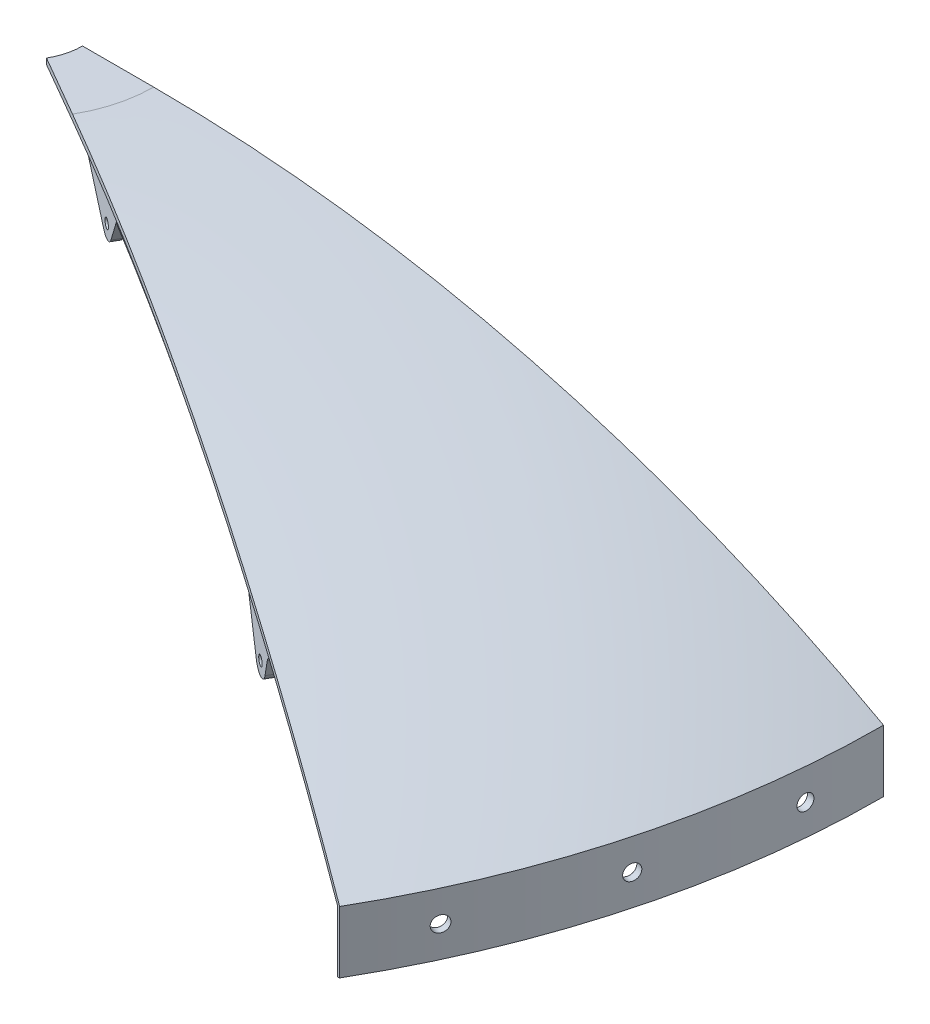
SolidWorks part; units mm, degrees
note: '?' marks a value the reader was unsure of.
other "Markup1"
sketch "Sketch6" plane through (25, -0.5009, 1.5) normal (-0.1086, 0.112, 0.9878) x (0.8685, -0.4727, 0.1491)
ref_plane "Front Plane" through (0, 0, 0) normal (0, 0, 1) x (1, 0, 0)
ref_plane "Top Plane" through (0, 0, 0) normal (0, 1, 0) x (1, 0, 0)
ref_plane "Right Plane" through (0, 0, 0) normal (1, 0, 0) x (0, 0, -1)
sketch "Sketch1" plane through (0, 0, 0) normal (0, 0, 1) x (1, 0, 0)
  line L0 (-45, 0) -> (45, 0) construction
  line L1 (300, -65.3534) -> (300, -85.3534)
  line L2 (-45, -150.7069) -> (45, -150.7069) construction
  line L3 (-45, 0) -> (-45, -150.7069) construction
  line L4 (45, 0) -> (45, -150.7069) construction
  line L5 (0, 0) -> (0, -150.7069)
  line L6 (45, 0) -> (0, 0)
  line L7 (0, -150.7069) -> (45, -150.7069)
  arc A0 (45, 0) -> (300, -65.3534) centre (45, -530.1639) cw
  arc A1 (-28.1177, 0) -> (35.3823, 0) centre (3.6323, -0.0236) cw construction
  arc A2 (45, -150.7069) -> (300, -85.3534) centre (45, 379.457) ccw
  point P4 (0, 0)
  dimension "D2" = 300
  dimension "D3" = 31.75
  dimension "D5" = 150.7069
  dimension "D1" = 90
  dimension "D4" = 20
sketch "Sketch2" plane through (0, 0, 0) normal (0, 0, 1) x (1, 0, 0)
  line L0 (299.5, -67.3534) -> (293.5, -67.3534)
  line L1 (291.5, -69.3534) -> (291.5, -85.6495)
  line L2 (54.9033, -10.5962) -> (27, -10.5962)
  line L3 (25, -8.5962) -> (25, -5.5)
  line L4 (300, -65.3534) -> (300, -85.3534) construction
  line L5 (300, -65.3534) -> (300, -85.3534) construction
  line L6 (299.5, -65.6495) -> (299.5, -67.3534)
  line L7 (291.5, -85.6495) -> (271.5, -85.6495)
  line L8 (45, -1.5009) -> (45, -3.5)
  line L9 (45, 0) -> (45, -150.7069) construction
  line L10 (45, -3.5) -> (27, -3.5)
  line L11 (271.5, -85.6495) -> (271.5, -65.6032)
  line L12 (45, -0.5) -> (0.5, -0.5)
  line L13 (0.5, -0.5) -> (0.5, -150.2069)
  line L14 (0.5, -150.2069) -> (45, -150.2069)
  line L15 (299.5, -85.0574) -> (299.5, -65.6495)
  line L20 (55, -13.5) -> (25, -13.5) construction
  line L21 (55, -10.5962) -> (55, -13.5) construction
  line L22 (140, -19.2573) -> (140, -23.2573)
  line L23 (140, -19.2573) -> (126, -19.2573)
  line L24 (125, -18.2573) -> (125, -17.5517)
  line L25 (141, -24.2573) -> (163.7816, -24.2573)
  line L26 (0, 0) -> (0, -150.7069) construction
  line L27 (45, -3.5) -> (25, -3.5) construction
  line L28 (45, -0.5) -> (45, -3.5) construction
  arc A0 (268.6519, -61.0899) -> (163.7816, -24.2573) centre (45, -530.1639) ccw
  arc A1 (294.6951, -74.4195) -> (55, -10.5962) centre (45, -530.1639) ccw construction
  arc A2 (55.0976, -10.5981) -> (54.9033, -10.5962) centre (54.9033, -20.5962) ccw
  arc A3 (271.5, -65.6032) -> (268.6519, -61.0899) centre (266.5, -65.6032) ccw
  arc A4 (293.5, -67.3534) -> (291.5, -69.3534) centre (293.5, -69.3534) ccw
  arc A5 (124.1523, -16.5634) -> (55.0976, -10.5981) centre (45, -530.1639) ccw
  arc A6 (45, -150.2069) -> (299.5, -85.0574) centre (45, 379.457) ccw
  arc A7 (299.5, -65.6495) -> (45, -0.5) centre (45, -530.1639) ccw
  arc A9 (299.5, -65.6495) -> (46.0019, -0.5009) centre (45, -530.1639) ccw
  arc A10 (125, -16.6947) -> (163.7816, -24.2573) centre (45, -530.1639) cw construction
  arc A11 (140, -23.2573) -> (141, -24.2573) centre (141, -23.2573) ccw
  arc A12 (126, -19.2573) -> (125, -18.2573) centre (126, -18.2573) cw
  arc A13 (125, -17.5517) -> (124.1523, -16.5634) centre (124, -17.5517) ccw
  arc A14 (27, -10.5962) -> (25, -8.5962) centre (27, -8.5962) cw
  arc A15 (27, -3.5) -> (25, -5.5) centre (27, -5.5) ccw
  arc A16 (299.5, -65.6495) -> (45, -0.5) centre (45, -530.1639) ccw construction
  arc A17 (45, -1.5009) -> (46.0019, -0.5009) centre (46, -1.5009) cw
  point P26 (300, -75.3534)
  point P33 (291.5, -67.3534)
  point P43 (140, -24.2573)
  point P48 (125, -19.2573)
  point P57 (25, -3.5)
  dimension "D5" = 10
  dimension "D10" = 5
  dimension "D11" = 2
  dimension "D16" = 1
  dimension "D17" = 2
  dimension "D18" = 1
  dimension "D2" = 20
  dimension "D3" = 3
  dimension "D6" = 7.0962
  dimension "D7" = 8
  dimension "D8" = 8
  dimension "D9" = 20
  dimension "D12" = 20
  dimension "D13" = 15
  dimension "D14" = 5
  dimension "D15" = 140
  dimension "D1" = 0.5
  dimension "D4" = 10
sketch "Sketch7" plane through (0, 0, 0) normal (0, 0, 1) x (1, 0, 0)
  line L4 (45, 1.5) -> (0, 1.5)
  line L11 (301.5, -86.2406) -> (301.5, -64.4663)
  line L12 (299.5, -85.0574) -> (299.5, -65.6495)
  line L13 (0.5, -150.2069) -> (45, -150.2069)
  line L14 (0.5, -0.5) -> (0.5, -150.2069)
  line L15 (45, -0.5) -> (0.5, -0.5)
  line L16 (299.5, -85.0574) -> (299.5, -65.6495)
  line L19 (45, -0.5) -> (0.5, -0.5)
  line L20 (299.5, -85.0574) -> (299.5, -87.3366)
  line L21 (0.5, -0.5) -> (0, -0.5)
  line L22 (0.5, -0.5) -> (0.5, -150.2069) construction
  line L23 (-1.5, 1.5) -> (-1.5, -152.2069) construction
  line L24 (0, 0) -> (0, -150.7069) construction
  line L25 (0, -0.5) -> (0, 1.5)
  line L26 (45, 1.5) -> (-1.5, 1.5) construction
  line L27 (0.5, -150.2069) -> (45, -150.2069) construction
  line L28 (-1.5, -152.2069) -> (45, -152.2069) construction
  arc A2 (301.5, -64.4663) -> (45, 1.5) centre (45, -530.1639) ccw
  arc A3 (299.5, -87.3366) -> (301.5, -86.2406) centre (45, 379.457) ccw
  arc A6 (45, -150.2069) -> (299.5, -85.0574) centre (45, 379.457) ccw
  arc A7 (299.5, -65.6495) -> (45, -0.5) centre (45, -530.1639) ccw
  arc A9 (299.5, -65.6495) -> (45, -0.5) centre (45, -530.1639) ccw
  arc A10 (45, -150.2069) -> (299.5, -85.0574) centre (45, 379.457) ccw construction
  arc A11 (45, -152.2069) -> (301.5, -86.2406) centre (45, 379.457) ccw construction
  dimension "D1" = 0.5
  dimension "D2" = 2
revolve "Revolve1" add sketch "Sketch7" angle 30 about L5
sketch "Sketch8" plane through (0, 1.5, 0) normal (0, 1, 0) x (1, 0, 0)
  circle A0 centre (0, 0) radius 20
  dimension "D1" = 40
extrude "Cut-Extrude1" cut sketch "Sketch8" against normal blind 10
ref_plane "Plane1" through (0, 0, 1.6) normal (0, 0, -1) x (-1, 0, 0)
sketch "Sketch9" plane through (0, 0, 1.6) normal (0, 0, -1) x (-1, 0, 0)
  line L0 (-292.7813, -61.4655) -> (-279.6691, -61.4655)
  line L1 (-47.4774, -0.0058) -> (-55.419, -6.1036)
  line L2 (-232.6747, -45.4182) -> (-218.4827, -40.3043) construction
  line L3 (-219.4729, -45.9758) -> (-221.1679, -41.2719) construction
  line L4 (-215.8237, -48.8578) -> (-208.4239, -33.1209)
  line L5 (-223.8476, -47.5522) -> (-226.0321, -41.4899)
  line L6 (-72.229, -6.7077) -> (-71.8653, -13.6983) construction
  line L7 (45.2148, -0.5986) -> (-72.229, -6.7077) construction
  line L8 (-69.1485, -17.472) -> (-55.419, -6.1036)
  line L9 (-75.885, -16.0359) -> (-81.0014, -7.2378)
  line L10 (-151.6575, -10.8394) -> (-189.6727, -12.8169) construction
  arc A0 (-45, 0) -> (-300, -65.3534) centre (-45, -530.1639) ccw construction
  arc A1 (-45, 0) -> (-292.7813, -61.4655) centre (-45, -530.1639) ccw
  circle A5 centre (-219.4729, -45.9758) radius 1.65
  circle A6 centre (-71.8653, -13.6983) radius 1.65
  arc A8 (-163.7816, -24.2573) -> (-268.6519, -61.0899) centre (-45, -530.1639) ccw construction
  arc A9 (-223.8476, -47.5522) -> (-214.9257, -46.9479) centre (-219.4729, -45.9758) ccw
  arc A10 (-229.9127, -39.6998) -> (-279.6691, -61.4655) centre (-45, -530.1639) ccw
  arc A11 (-208.4239, -33.1209) -> (-206.6342, -31.5436) centre (-205.7091, -34.3974) cw
  arc A12 (-226.0321, -41.4899) -> (-229.9127, -39.6998) centre (-228.8544, -42.5069) ccw
  arc A13 (-75.885, -16.0359) -> (-68.6644, -17.0712) centre (-71.8653, -13.6983) ccw
  arc A14 (-81.0014, -7.2378) -> (-206.6342, -31.5436) centre (-45, -530.1639) ccw
  point P29 (-227.0611, -38.6341)
  dimension "D2" = 3.3
  dimension "D3" = 5
  dimension "D4" = 3
  dimension "D6" = 3
  dimension "D8" = 3
  dimension "D5" = 45
  dimension "D7" = 7
extrude "Boss-Extrude1" add sketch "Sketch9" against normal blind 3 contours A14 L9 A13 L8 L1 A1 L0 A10 A12 L5 A9 L4 A11 A6 A5
ref_plane "Plane2" through (0, 0, 0) normal (0.2588, 0, -0.9659) x (-0.9659, 0, -0.2588)
mirror "Mirror1" about plane through (0, 0, 0) normal (0.2588, 0, -0.9659) of "Boss-Extrude1"
ref_axis "Axis1" through (0, 0, 0) along (0, 1, 0)?
ref_plane "Plane3" through (0, 0, 0) normal (0.0872, 0, -0.9962) x (0, 1, 0)
ref_plane "Plane4" through (300.3527, 0, 26.2775) normal (0.9962, 0, 0.0872) x (0.0872, 0, -0.9962)
ref_plane "Plane5" through (0, -64.4663, 0) normal (0, 1, 0) x (1, 0, 0)
ref_plane "Plane6" through (0, -86.2406, 0) normal (0, 1, 0) x (1, 0, 0)
ref_plane "Plane7" through (0, -75.3534, 0) normal (0, 1, 0) x (1, 0, 0)
sketch "Sketch11" plane through (0, -75.3534, 0) normal (0, 1, 0) x (1, 0, 0)
  line L0 (296.3545, -43.2926) -> (299.3699, -8.8266)
  line L1 (54.3019, -4.7508) -> (-54.3019, 4.7508) construction
  arc A0 (259.3746, -149.75) -> (299.5, 0) centre (0, 0) ccw construction
  arc A1 (296.3545, -43.2926) -> (299.3699, -8.8266) centre (0, 0) ccw
  point P8 (300.3527, -26.2775)
  point P9 (0, 0)
  dimension "D1" = 2.5
extrude "Boss-Extrude2" add sketch "Sketch11" against normal mid plane 15
sketch "Sketch10" plane through (300.3527, 0, 26.2775) normal (0.9962, 0, 0.0872) x (0.0872, 0, -0.9962)
  line L0 (-127.4194, -64.4663) -> (26.2775, -64.4663) construction
  line L1 (-127.4194, -86.2406) -> (26.2775, -86.2406) construction
  line L2 (-127.4194, -64.4663) -> (26.2775, -64.4663) construction
  line L3 (-127.4194, -86.2406) -> (26.2775, -86.2406) construction
  line L4 (0, -86.2406) -> (0, -64.4663) construction
  line L5 (0, -54.5094) -> (0, 54.5094) construction
  circle A0 centre (0, -75.3534) radius 2.75
  point P9 (0, 0)
  dimension "D1" = 5.5
extrude "Cut-Extrude2" cut sketch "Sketch10" against normal through all
pattern_circular "CirPattern1" count 3 every 10 about axis through (0, 0, 0) along (0, 1, 0) of "Boss-Extrude2", "Cut-Extrude2"
